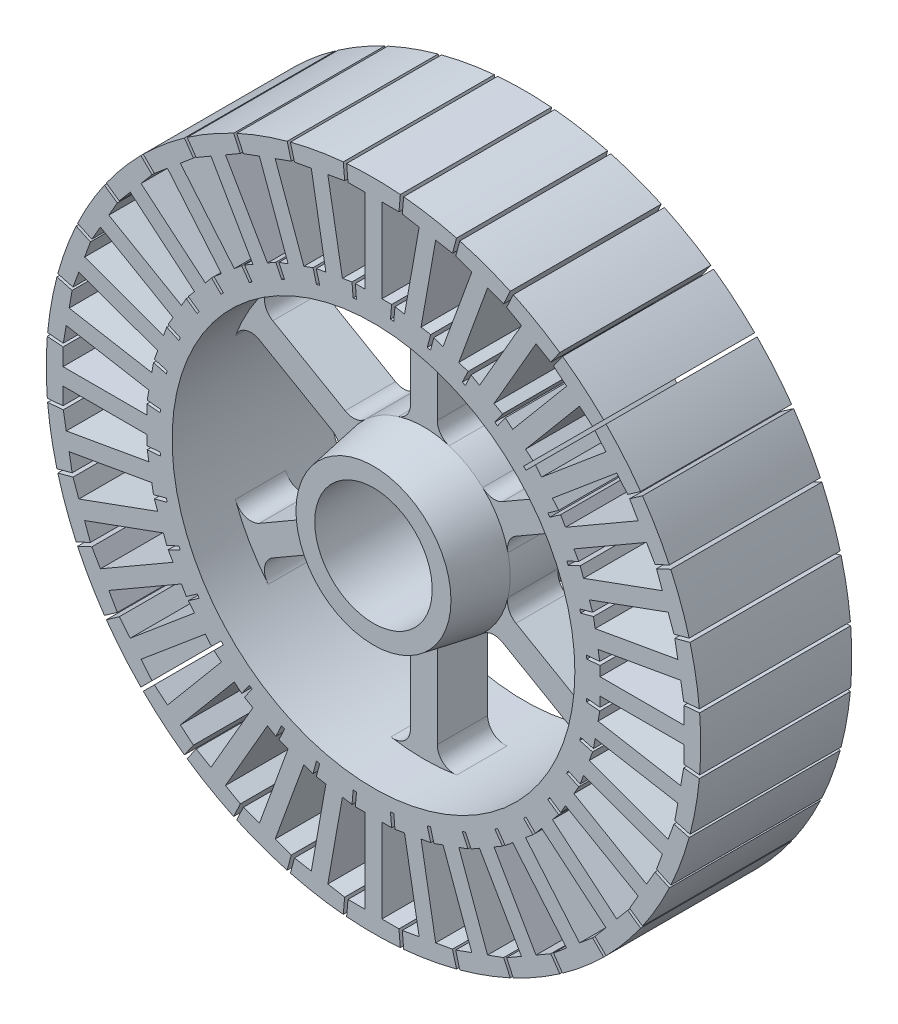
SolidWorks part; units mm, degrees
material "Нержавеющая сталь (ферритная)"
ref_plane "Спереди" through (0, 0, 0) normal (0, 0, 1) x (1, 0, 0)
ref_plane "Сверху" through (0, 0, 0) normal (0, 1, 0) x (1, 0, 0)
ref_plane "Справа" through (0, 0, 0) normal (1, 0, 0) x (0, 0, -1)
sketch "Эскиз1" plane through (0, 0, 0) normal (0, 0, 1) x (1, 0, 0)
  circle A0 centre (0, 0) radius 17.5
  circle A1 centre (0, 0) radius 97.5
  dimension "D1" = 35
  dimension "D2" = 195
extrude "Бобышка-Вытянуть1" add sketch "Эскиз1" along normal blind 45
sketch "Эскиз2" plane through (0, 0, 45) normal (0, 0, 1) x (1, 0, 0)
  line L0 (0, 0) -> (0, 97.5) construction
  line L1 (0, 0) -> (8.4977, 97.129) construction
  line L2 (0, 0) -> (-8.4977, 97.129) construction
  line L3 (-8.0518, 97.769) -> (-7.5908, 92.5)
  line L4 (-2.5, 92.5) -> (2.5, 92.5) construction
  line L5 (-2.5, 92.5) -> (-2.5, 67.5) construction
  line L6 (-2.5, 67.5) -> (2.5, 67.5) construction
  line L7 (2.5, 92.5) -> (2.5, 67.5) construction
  line L8 (0, 67.5) -> (0, 92.5) construction
  line L9 (-2.5, 80) -> (2.5, 80) construction
  line L10 (-7.5908, 92.5) -> (-2.5, 92.5)
  line L11 (-9.048, 97.6818) -> (-8.587, 92.4128)
  line L12 (-2.5, 67.5) -> (-5.4036, 67.5)
  line L13 (-5.4036, 67.5) -> (-5.0578, 63.5478)
  line L14 (-5.0578, 63.5478) -> (-6.054, 63.4607)
  line L15 (-2.5, 92.5) -> (-2.5, 67.5)
  line L16 (-8.587, 92.4128) -> (-13.6004, 91.5288)
  line L17 (-13.6004, 91.5288) -> (-9.2592, 66.9086)
  line L18 (-9.2592, 66.9086) -> (-6.3998, 67.4128)
  line L19 (-6.3998, 67.4128) -> (-6.054, 63.4607)
  line L20 (-8.0518, 97.769) -> (-9.048, 97.6818)
  line L21 (9.048, 97.6818) -> (8.0518, 97.769)
  line L22 (8.0518, 97.769) -> (7.5908, 92.5)
  line L23 (7.5908, 92.5) -> (2.5, 92.5)
  line L24 (2.5, 92.5) -> (2.5, 67.5)
  line L25 (2.5, 67.5) -> (5.4036, 67.5)
  line L26 (5.4036, 67.5) -> (5.0578, 63.5478)
  line L27 (6.054, 63.4607) -> (5.0578, 63.5478)
  line L28 (6.3998, 67.4128) -> (6.054, 63.4607)
  line L29 (9.2592, 66.9086) -> (6.3998, 67.4128)
  line L30 (13.6004, 91.5288) -> (9.2592, 66.9086)
  line L31 (8.587, 92.4128) -> (13.6004, 91.5288)
  line L32 (9.048, 97.6818) -> (8.587, 92.4128)
  line L33 (25.8728, 94.6267) -> (24.9068, 94.8855)
  line L34 (24.9068, 94.8855) -> (23.5379, 89.7766)
  line L35 (23.5379, 89.7766) -> (18.5245, 90.6606)
  line L36 (18.5245, 90.6606) -> (14.1833, 66.0404)
  line L37 (14.1833, 66.0404) -> (17.0427, 65.5362)
  line L38 (17.0427, 65.5362) -> (16.0159, 61.7041)
  line L39 (16.9819, 61.4453) -> (16.0159, 61.7041)
  line L40 (18.0087, 65.2774) -> (16.9819, 61.4453)
  line L41 (20.7371, 64.2843) -> (18.0087, 65.2774)
  line L42 (29.2876, 87.7766) -> (20.7371, 64.2843)
  line L43 (24.5039, 89.5178) -> (29.2876, 87.7766)
  line L44 (25.8728, 94.6267) -> (24.5039, 89.5178)
  line L45 (41.9115, 88.6963) -> (41.0051, 89.1189)
  line L46 (41.0051, 89.1189) -> (38.7699, 84.3254)
  line L47 (38.7699, 84.3254) -> (33.9861, 86.0665)
  line L48 (33.9861, 86.0665) -> (25.4356, 62.5742)
  line L49 (25.4356, 62.5742) -> (28.1641, 61.5811)
  line L50 (28.1641, 61.5811) -> (26.4874, 57.9856)
  line L51 (27.3937, 57.563) -> (26.4874, 57.9856)
  line L52 (29.0704, 61.1585) -> (27.3937, 57.563)
  line L53 (31.5849, 59.7067) -> (29.0704, 61.1585)
  line L54 (44.0849, 81.3573) -> (31.5849, 59.7067)
  line L55 (39.6762, 83.9027) -> (44.0849, 81.3573)
  line L56 (41.9115, 88.6963) -> (39.6762, 83.9027)
  line L57 (56.6767, 80.071) -> (55.8575, 80.6445)
  line L58 (55.8575, 80.6445) -> (52.8238, 76.312)
  line L59 (52.8238, 76.312) -> (48.4151, 78.8573)
  line L60 (48.4151, 78.8573) -> (35.9151, 57.2067)
  line L61 (35.9151, 57.2067) -> (38.4296, 55.7549)
  line L62 (38.4296, 55.7549) -> (36.1541, 52.5051)
  line L63 (36.9733, 51.9316) -> (36.1541, 52.5051)
  line L64 (39.2488, 55.1814) -> (36.9733, 51.9316)
  line L65 (41.4731, 53.315) -> (39.2488, 55.1814)
  line L66 (57.5427, 72.4661) -> (41.4731, 53.315)
  line L67 (53.643, 75.7384) -> (57.5427, 72.4661)
  line L68 (56.6767, 80.071) -> (53.643, 75.7384)
  line L69 (69.7198, 69.0127) -> (69.0127, 69.7198)
  line L70 (69.0127, 69.7198) -> (65.2727, 65.9798)
  line L71 (65.2727, 65.9798) -> (61.373, 69.2521)
  line L72 (61.373, 69.2521) -> (45.3033, 50.101)
  line L73 (45.3033, 50.101) -> (47.5275, 48.2346)
  line L74 (47.5275, 48.2346) -> (44.7223, 45.4294)
  line L75 (45.4294, 44.7223) -> (44.7223, 45.4294)
  line L76 (48.2346, 47.5275) -> (45.4294, 44.7223)
  line L77 (50.101, 45.3033) -> (48.2346, 47.5275)
  line L78 (69.2521, 61.373) -> (50.101, 45.3033)
  line L79 (65.9798, 65.2727) -> (69.2521, 61.373)
  line L80 (69.7198, 69.0127) -> (65.9798, 65.2727)
  line L81 (80.6445, 55.8575) -> (80.071, 56.6767)
  line L82 (80.071, 56.6767) -> (75.7384, 53.643)
  line L83 (75.7384, 53.643) -> (72.4661, 57.5427)
  line L84 (72.4661, 57.5427) -> (53.315, 41.4731)
  line L85 (53.315, 41.4731) -> (55.1814, 39.2488)
  line L86 (55.1814, 39.2488) -> (51.9316, 36.9733)
  line L87 (52.5051, 36.1541) -> (51.9316, 36.9733)
  line L88 (55.7549, 38.4296) -> (52.5051, 36.1541)
  line L89 (57.2067, 35.9151) -> (55.7549, 38.4296)
  line L90 (78.8573, 48.4151) -> (57.2067, 35.9151)
  line L91 (76.312, 52.8238) -> (78.8573, 48.4151)
  line L92 (80.6445, 55.8575) -> (76.312, 52.8238)
  line L93 (89.1189, 41.0051) -> (88.6963, 41.9115)
  line L94 (88.6963, 41.9115) -> (83.9027, 39.6762)
  line L95 (83.9027, 39.6762) -> (81.3573, 44.0849)
  line L96 (81.3573, 44.0849) -> (59.7067, 31.5849)
  line L97 (59.7067, 31.5849) -> (61.1585, 29.0704)
  line L98 (61.1585, 29.0704) -> (57.563, 27.3937)
  line L99 (57.9856, 26.4874) -> (57.563, 27.3937)
  line L100 (61.5811, 28.1641) -> (57.9856, 26.4874)
  line L101 (62.5742, 25.4356) -> (61.5811, 28.1641)
  line L102 (86.0665, 33.9861) -> (62.5742, 25.4356)
  line L103 (84.3254, 38.7699) -> (86.0665, 33.9861)
  line L104 (89.1189, 41.0051) -> (84.3254, 38.7699)
  line L105 (94.8855, 24.9068) -> (94.6267, 25.8728)
  line L106 (94.6267, 25.8728) -> (89.5178, 24.5039)
  line L107 (89.5178, 24.5039) -> (87.7766, 29.2876)
  line L108 (87.7766, 29.2876) -> (64.2843, 20.7371)
  line L109 (64.2843, 20.7371) -> (65.2774, 18.0087)
  line L110 (65.2774, 18.0087) -> (61.4453, 16.9819)
  line L111 (61.7041, 16.0159) -> (61.4453, 16.9819)
  line L112 (65.5362, 17.0427) -> (61.7041, 16.0159)
  line L113 (66.0404, 14.1833) -> (65.5362, 17.0427)
  line L114 (90.6606, 18.5245) -> (66.0404, 14.1833)
  line L115 (89.7766, 23.5379) -> (90.6606, 18.5245)
  line L116 (94.8855, 24.9068) -> (89.7766, 23.5379)
  line L117 (97.769, 8.0518) -> (97.6818, 9.048)
  line L118 (97.6818, 9.048) -> (92.4128, 8.587)
  line L119 (92.4128, 8.587) -> (91.5288, 13.6004)
  line L120 (91.5288, 13.6004) -> (66.9086, 9.2592)
  line L121 (66.9086, 9.2592) -> (67.4128, 6.3998)
  line L122 (67.4128, 6.3998) -> (63.4607, 6.054)
  line L123 (63.5478, 5.0578) -> (63.4607, 6.054)
  line L124 (67.5, 5.4036) -> (63.5478, 5.0578)
  line L125 (67.5, 2.5) -> (67.5, 5.4036)
  line L126 (92.5, 2.5) -> (67.5, 2.5)
  line L127 (92.5, 7.5908) -> (92.5, 2.5)
  line L128 (97.769, 8.0518) -> (92.5, 7.5908)
  line L129 (97.6818, -9.048) -> (97.769, -8.0518)
  line L130 (97.769, -8.0518) -> (92.5, -7.5908)
  line L131 (92.5, -7.5908) -> (92.5, -2.5)
  line L132 (92.5, -2.5) -> (67.5, -2.5)
  line L133 (67.5, -2.5) -> (67.5, -5.4036)
  line L134 (67.5, -5.4036) -> (63.5478, -5.0578)
  line L135 (63.4607, -6.054) -> (63.5478, -5.0578)
  line L136 (67.4128, -6.3998) -> (63.4607, -6.054)
  line L137 (66.9086, -9.2592) -> (67.4128, -6.3998)
  line L138 (91.5288, -13.6004) -> (66.9086, -9.2592)
  line L139 (92.4128, -8.587) -> (91.5288, -13.6004)
  line L140 (97.6818, -9.048) -> (92.4128, -8.587)
  line L141 (94.6267, -25.8728) -> (94.8855, -24.9068)
  line L142 (94.8855, -24.9068) -> (89.7766, -23.5379)
  line L143 (89.7766, -23.5379) -> (90.6606, -18.5245)
  line L144 (90.6606, -18.5245) -> (66.0404, -14.1833)
  line L145 (66.0404, -14.1833) -> (65.5362, -17.0427)
  line L146 (65.5362, -17.0427) -> (61.7041, -16.0159)
  line L147 (61.4453, -16.9819) -> (61.7041, -16.0159)
  line L148 (65.2774, -18.0087) -> (61.4453, -16.9819)
  line L149 (64.2843, -20.7371) -> (65.2774, -18.0087)
  line L150 (87.7766, -29.2876) -> (64.2843, -20.7371)
  line L151 (89.5178, -24.5039) -> (87.7766, -29.2876)
  line L152 (94.6267, -25.8728) -> (89.5178, -24.5039)
  line L153 (88.6963, -41.9115) -> (89.1189, -41.0051)
  line L154 (89.1189, -41.0051) -> (84.3254, -38.7699)
  line L155 (84.3254, -38.7699) -> (86.0665, -33.9861)
  line L156 (86.0665, -33.9861) -> (62.5742, -25.4356)
  line L157 (62.5742, -25.4356) -> (61.5811, -28.1641)
  line L158 (61.5811, -28.1641) -> (57.9856, -26.4874)
  line L159 (57.563, -27.3937) -> (57.9856, -26.4874)
  line L160 (61.1585, -29.0704) -> (57.563, -27.3937)
  line L161 (59.7067, -31.5849) -> (61.1585, -29.0704)
  line L162 (81.3573, -44.0849) -> (59.7067, -31.5849)
  line L163 (83.9027, -39.6762) -> (81.3573, -44.0849)
  line L164 (88.6963, -41.9115) -> (83.9027, -39.6762)
  line L165 (80.071, -56.6767) -> (80.6445, -55.8575)
  line L166 (80.6445, -55.8575) -> (76.312, -52.8238)
  line L167 (76.312, -52.8238) -> (78.8573, -48.4151)
  line L168 (78.8573, -48.4151) -> (57.2067, -35.9151)
  line L169 (57.2067, -35.9151) -> (55.7549, -38.4296)
  line L170 (55.7549, -38.4296) -> (52.5051, -36.1541)
  line L171 (51.9316, -36.9733) -> (52.5051, -36.1541)
  line L172 (55.1814, -39.2488) -> (51.9316, -36.9733)
  line L173 (53.315, -41.4731) -> (55.1814, -39.2488)
  line L174 (72.4661, -57.5427) -> (53.315, -41.4731)
  line L175 (75.7384, -53.643) -> (72.4661, -57.5427)
  line L176 (80.071, -56.6767) -> (75.7384, -53.643)
  line L177 (69.0127, -69.7198) -> (69.7198, -69.0127)
  line L178 (69.7198, -69.0127) -> (65.9798, -65.2727)
  line L179 (65.9798, -65.2727) -> (69.2521, -61.373)
  line L180 (69.2521, -61.373) -> (50.101, -45.3033)
  line L181 (50.101, -45.3033) -> (48.2346, -47.5275)
  line L182 (48.2346, -47.5275) -> (45.4294, -44.7223)
  line L183 (44.7223, -45.4294) -> (45.4294, -44.7223)
  line L184 (47.5275, -48.2346) -> (44.7223, -45.4294)
  line L185 (45.3033, -50.101) -> (47.5275, -48.2346)
  line L186 (61.373, -69.2521) -> (45.3033, -50.101)
  line L187 (65.2727, -65.9798) -> (61.373, -69.2521)
  line L188 (69.0127, -69.7198) -> (65.2727, -65.9798)
  line L189 (55.8575, -80.6445) -> (56.6767, -80.071)
  line L190 (56.6767, -80.071) -> (53.643, -75.7384)
  line L191 (53.643, -75.7384) -> (57.5427, -72.4661)
  line L192 (57.5427, -72.4661) -> (41.4731, -53.315)
  line L193 (41.4731, -53.315) -> (39.2488, -55.1814)
  line L194 (39.2488, -55.1814) -> (36.9733, -51.9316)
  line L195 (36.1541, -52.5051) -> (36.9733, -51.9316)
  line L196 (38.4296, -55.7549) -> (36.1541, -52.5051)
  line L197 (35.9151, -57.2067) -> (38.4296, -55.7549)
  line L198 (48.4151, -78.8573) -> (35.9151, -57.2067)
  line L199 (52.8238, -76.312) -> (48.4151, -78.8573)
  line L200 (55.8575, -80.6445) -> (52.8238, -76.312)
  line L201 (41.0051, -89.1189) -> (41.9115, -88.6963)
  line L202 (41.9115, -88.6963) -> (39.6762, -83.9027)
  line L203 (39.6762, -83.9027) -> (44.0849, -81.3573)
  line L204 (44.0849, -81.3573) -> (31.5849, -59.7067)
  line L205 (31.5849, -59.7067) -> (29.0704, -61.1585)
  line L206 (29.0704, -61.1585) -> (27.3937, -57.563)
  line L207 (26.4874, -57.9856) -> (27.3937, -57.563)
  line L208 (28.1641, -61.5811) -> (26.4874, -57.9856)
  line L209 (25.4356, -62.5742) -> (28.1641, -61.5811)
  line L210 (33.9861, -86.0665) -> (25.4356, -62.5742)
  line L211 (38.7699, -84.3254) -> (33.9861, -86.0665)
  line L212 (41.0051, -89.1189) -> (38.7699, -84.3254)
  line L213 (24.9068, -94.8855) -> (25.8728, -94.6267)
  line L214 (25.8728, -94.6267) -> (24.5039, -89.5178)
  line L215 (24.5039, -89.5178) -> (29.2876, -87.7766)
  line L216 (29.2876, -87.7766) -> (20.7371, -64.2843)
  line L217 (20.7371, -64.2843) -> (18.0087, -65.2774)
  line L218 (18.0087, -65.2774) -> (16.9819, -61.4453)
  line L219 (16.0159, -61.7041) -> (16.9819, -61.4453)
  line L220 (17.0427, -65.5362) -> (16.0159, -61.7041)
  line L221 (14.1833, -66.0404) -> (17.0427, -65.5362)
  line L222 (18.5245, -90.6606) -> (14.1833, -66.0404)
  line L223 (23.5379, -89.7766) -> (18.5245, -90.6606)
  line L224 (24.9068, -94.8855) -> (23.5379, -89.7766)
  line L225 (8.0518, -97.769) -> (9.048, -97.6818)
  line L226 (9.048, -97.6818) -> (8.587, -92.4128)
  line L227 (8.587, -92.4128) -> (13.6004, -91.5288)
  line L228 (13.6004, -91.5288) -> (9.2592, -66.9086)
  line L229 (9.2592, -66.9086) -> (6.3998, -67.4128)
  line L230 (6.3998, -67.4128) -> (6.054, -63.4607)
  line L231 (5.0578, -63.5478) -> (6.054, -63.4607)
  line L232 (5.4036, -67.5) -> (5.0578, -63.5478)
  line L233 (2.5, -67.5) -> (5.4036, -67.5)
  line L234 (2.5, -92.5) -> (2.5, -67.5)
  line L235 (7.5908, -92.5) -> (2.5, -92.5)
  line L236 (8.0518, -97.769) -> (7.5908, -92.5)
  line L237 (-9.048, -97.6818) -> (-8.0518, -97.769)
  line L238 (-8.0518, -97.769) -> (-7.5908, -92.5)
  line L239 (-7.5908, -92.5) -> (-2.5, -92.5)
  line L240 (-2.5, -92.5) -> (-2.5, -67.5)
  line L241 (-2.5, -67.5) -> (-5.4036, -67.5)
  line L242 (-5.4036, -67.5) -> (-5.0578, -63.5478)
  line L243 (-6.054, -63.4607) -> (-5.0578, -63.5478)
  line L244 (-6.3998, -67.4128) -> (-6.054, -63.4607)
  line L245 (-9.2592, -66.9086) -> (-6.3998, -67.4128)
  line L246 (-13.6004, -91.5288) -> (-9.2592, -66.9086)
  line L247 (-8.587, -92.4128) -> (-13.6004, -91.5288)
  line L248 (-9.048, -97.6818) -> (-8.587, -92.4128)
  line L249 (-25.8728, -94.6267) -> (-24.9068, -94.8855)
  line L250 (-24.9068, -94.8855) -> (-23.5379, -89.7766)
  line L251 (-23.5379, -89.7766) -> (-18.5245, -90.6606)
  line L252 (-18.5245, -90.6606) -> (-14.1833, -66.0404)
  line L253 (-14.1833, -66.0404) -> (-17.0427, -65.5362)
  line L254 (-17.0427, -65.5362) -> (-16.0159, -61.7041)
  line L255 (-16.9819, -61.4453) -> (-16.0159, -61.7041)
  line L256 (-18.0087, -65.2774) -> (-16.9819, -61.4453)
  line L257 (-20.7371, -64.2843) -> (-18.0087, -65.2774)
  line L258 (-29.2876, -87.7766) -> (-20.7371, -64.2843)
  line L259 (-24.5039, -89.5178) -> (-29.2876, -87.7766)
  line L260 (-25.8728, -94.6267) -> (-24.5039, -89.5178)
  line L261 (-41.9115, -88.6963) -> (-41.0051, -89.1189)
  line L262 (-41.0051, -89.1189) -> (-38.7699, -84.3254)
  line L263 (-38.7699, -84.3254) -> (-33.9861, -86.0665)
  line L264 (-33.9861, -86.0665) -> (-25.4356, -62.5742)
  line L265 (-25.4356, -62.5742) -> (-28.1641, -61.5811)
  line L266 (-28.1641, -61.5811) -> (-26.4874, -57.9856)
  line L267 (-27.3937, -57.563) -> (-26.4874, -57.9856)
  line L268 (-29.0704, -61.1585) -> (-27.3937, -57.563)
  line L269 (-31.5849, -59.7067) -> (-29.0704, -61.1585)
  line L270 (-44.0849, -81.3573) -> (-31.5849, -59.7067)
  line L271 (-39.6762, -83.9027) -> (-44.0849, -81.3573)
  line L272 (-41.9115, -88.6963) -> (-39.6762, -83.9027)
  line L273 (-56.6767, -80.071) -> (-55.8575, -80.6445)
  line L274 (-55.8575, -80.6445) -> (-52.8238, -76.312)
  line L275 (-52.8238, -76.312) -> (-48.4151, -78.8573)
  line L276 (-48.4151, -78.8573) -> (-35.9151, -57.2067)
  line L277 (-35.9151, -57.2067) -> (-38.4296, -55.7549)
  line L278 (-38.4296, -55.7549) -> (-36.1541, -52.5051)
  line L279 (-36.9733, -51.9316) -> (-36.1541, -52.5051)
  line L280 (-39.2488, -55.1814) -> (-36.9733, -51.9316)
  line L281 (-41.4731, -53.315) -> (-39.2488, -55.1814)
  line L282 (-57.5427, -72.4661) -> (-41.4731, -53.315)
  line L283 (-53.643, -75.7384) -> (-57.5427, -72.4661)
  line L284 (-56.6767, -80.071) -> (-53.643, -75.7384)
  line L285 (-69.7198, -69.0127) -> (-69.0127, -69.7198)
  line L286 (-69.0127, -69.7198) -> (-65.2727, -65.9798)
  line L287 (-65.2727, -65.9798) -> (-61.373, -69.2521)
  line L288 (-61.373, -69.2521) -> (-45.3033, -50.101)
  line L289 (-45.3033, -50.101) -> (-47.5275, -48.2346)
  line L290 (-47.5275, -48.2346) -> (-44.7223, -45.4294)
  line L291 (-45.4294, -44.7223) -> (-44.7223, -45.4294)
  line L292 (-48.2346, -47.5275) -> (-45.4294, -44.7223)
  line L293 (-50.101, -45.3033) -> (-48.2346, -47.5275)
  line L294 (-69.2521, -61.373) -> (-50.101, -45.3033)
  line L295 (-65.9798, -65.2727) -> (-69.2521, -61.373)
  line L296 (-69.7198, -69.0127) -> (-65.9798, -65.2727)
  line L297 (-80.6445, -55.8575) -> (-80.071, -56.6767)
  line L298 (-80.071, -56.6767) -> (-75.7384, -53.643)
  line L299 (-75.7384, -53.643) -> (-72.4661, -57.5427)
  line L300 (-72.4661, -57.5427) -> (-53.315, -41.4731)
  line L301 (-53.315, -41.4731) -> (-55.1814, -39.2488)
  line L302 (-55.1814, -39.2488) -> (-51.9316, -36.9733)
  line L303 (-52.5051, -36.1541) -> (-51.9316, -36.9733)
  line L304 (-55.7549, -38.4296) -> (-52.5051, -36.1541)
  line L305 (-57.2067, -35.9151) -> (-55.7549, -38.4296)
  line L306 (-78.8573, -48.4151) -> (-57.2067, -35.9151)
  line L307 (-76.312, -52.8238) -> (-78.8573, -48.4151)
  line L308 (-80.6445, -55.8575) -> (-76.312, -52.8238)
  line L309 (-89.1189, -41.0051) -> (-88.6963, -41.9115)
  line L310 (-88.6963, -41.9115) -> (-83.9027, -39.6762)
  line L311 (-83.9027, -39.6762) -> (-81.3573, -44.0849)
  line L312 (-81.3573, -44.0849) -> (-59.7067, -31.5849)
  line L313 (-59.7067, -31.5849) -> (-61.1585, -29.0704)
  line L314 (-61.1585, -29.0704) -> (-57.563, -27.3937)
  line L315 (-57.9856, -26.4874) -> (-57.563, -27.3937)
  line L316 (-61.5811, -28.1641) -> (-57.9856, -26.4874)
  line L317 (-62.5742, -25.4356) -> (-61.5811, -28.1641)
  line L318 (-86.0665, -33.9861) -> (-62.5742, -25.4356)
  line L319 (-84.3254, -38.7699) -> (-86.0665, -33.9861)
  line L320 (-89.1189, -41.0051) -> (-84.3254, -38.7699)
  line L321 (-94.8855, -24.9068) -> (-94.6267, -25.8728)
  line L322 (-94.6267, -25.8728) -> (-89.5178, -24.5039)
  line L323 (-89.5178, -24.5039) -> (-87.7766, -29.2876)
  line L324 (-87.7766, -29.2876) -> (-64.2843, -20.7371)
  line L325 (-64.2843, -20.7371) -> (-65.2774, -18.0087)
  line L326 (-65.2774, -18.0087) -> (-61.4453, -16.9819)
  line L327 (-61.7041, -16.0159) -> (-61.4453, -16.9819)
  line L328 (-65.5362, -17.0427) -> (-61.7041, -16.0159)
  line L329 (-66.0404, -14.1833) -> (-65.5362, -17.0427)
  line L330 (-90.6606, -18.5245) -> (-66.0404, -14.1833)
  line L331 (-89.7766, -23.5379) -> (-90.6606, -18.5245)
  line L332 (-94.8855, -24.9068) -> (-89.7766, -23.5379)
  line L333 (-97.769, -8.0518) -> (-97.6818, -9.048)
  line L334 (-97.6818, -9.048) -> (-92.4128, -8.587)
  line L335 (-92.4128, -8.587) -> (-91.5288, -13.6004)
  line L336 (-91.5288, -13.6004) -> (-66.9086, -9.2592)
  line L337 (-66.9086, -9.2592) -> (-67.4128, -6.3998)
  line L338 (-67.4128, -6.3998) -> (-63.4607, -6.054)
  line L339 (-63.5478, -5.0578) -> (-63.4607, -6.054)
  line L340 (-67.5, -5.4036) -> (-63.5478, -5.0578)
  line L341 (-67.5, -2.5) -> (-67.5, -5.4036)
  line L342 (-92.5, -2.5) -> (-67.5, -2.5)
  line L343 (-92.5, -7.5908) -> (-92.5, -2.5)
  line L344 (-97.769, -8.0518) -> (-92.5, -7.5908)
  line L345 (-97.6818, 9.048) -> (-97.769, 8.0518)
  line L346 (-97.769, 8.0518) -> (-92.5, 7.5908)
  line L347 (-92.5, 7.5908) -> (-92.5, 2.5)
  line L348 (-92.5, 2.5) -> (-67.5, 2.5)
  line L349 (-67.5, 2.5) -> (-67.5, 5.4036)
  line L350 (-67.5, 5.4036) -> (-63.5478, 5.0578)
  line L351 (-63.4607, 6.054) -> (-63.5478, 5.0578)
  line L352 (-67.4128, 6.3998) -> (-63.4607, 6.054)
  line L353 (-66.9086, 9.2592) -> (-67.4128, 6.3998)
  line L354 (-91.5288, 13.6004) -> (-66.9086, 9.2592)
  line L355 (-92.4128, 8.587) -> (-91.5288, 13.6004)
  line L356 (-97.6818, 9.048) -> (-92.4128, 8.587)
  line L357 (-94.6267, 25.8728) -> (-94.8855, 24.9068)
  line L358 (-94.8855, 24.9068) -> (-89.7766, 23.5379)
  line L359 (-89.7766, 23.5379) -> (-90.6606, 18.5245)
  line L360 (-90.6606, 18.5245) -> (-66.0404, 14.1833)
  line L361 (-66.0404, 14.1833) -> (-65.5362, 17.0427)
  line L362 (-65.5362, 17.0427) -> (-61.7041, 16.0159)
  line L363 (-61.4453, 16.9819) -> (-61.7041, 16.0159)
  line L364 (-65.2774, 18.0087) -> (-61.4453, 16.9819)
  line L365 (-64.2843, 20.7371) -> (-65.2774, 18.0087)
  line L366 (-87.7766, 29.2876) -> (-64.2843, 20.7371)
  line L367 (-89.5178, 24.5039) -> (-87.7766, 29.2876)
  line L368 (-94.6267, 25.8728) -> (-89.5178, 24.5039)
  line L369 (-88.6963, 41.9115) -> (-89.1189, 41.0051)
  line L370 (-89.1189, 41.0051) -> (-84.3254, 38.7699)
  line L371 (-84.3254, 38.7699) -> (-86.0665, 33.9861)
  line L372 (-86.0665, 33.9861) -> (-62.5742, 25.4356)
  line L373 (-62.5742, 25.4356) -> (-61.5811, 28.1641)
  line L374 (-61.5811, 28.1641) -> (-57.9856, 26.4874)
  line L375 (-57.563, 27.3937) -> (-57.9856, 26.4874)
  line L376 (-61.1585, 29.0704) -> (-57.563, 27.3937)
  line L377 (-59.7067, 31.5849) -> (-61.1585, 29.0704)
  line L378 (-81.3573, 44.0849) -> (-59.7067, 31.5849)
  line L379 (-83.9027, 39.6762) -> (-81.3573, 44.0849)
  line L380 (-88.6963, 41.9115) -> (-83.9027, 39.6762)
  line L381 (-80.071, 56.6767) -> (-80.6445, 55.8575)
  line L382 (-80.6445, 55.8575) -> (-76.312, 52.8238)
  line L383 (-76.312, 52.8238) -> (-78.8573, 48.4151)
  line L384 (-78.8573, 48.4151) -> (-57.2067, 35.9151)
  line L385 (-57.2067, 35.9151) -> (-55.7549, 38.4296)
  line L386 (-55.7549, 38.4296) -> (-52.5051, 36.1541)
  line L387 (-51.9316, 36.9733) -> (-52.5051, 36.1541)
  line L388 (-55.1814, 39.2488) -> (-51.9316, 36.9733)
  line L389 (-53.315, 41.4731) -> (-55.1814, 39.2488)
  line L390 (-72.4661, 57.5427) -> (-53.315, 41.4731)
  line L391 (-75.7384, 53.643) -> (-72.4661, 57.5427)
  line L392 (-80.071, 56.6767) -> (-75.7384, 53.643)
  line L393 (-69.0127, 69.7198) -> (-69.7198, 69.0127)
  line L394 (-69.7198, 69.0127) -> (-65.9798, 65.2727)
  line L395 (-65.9798, 65.2727) -> (-69.2521, 61.373)
  line L396 (-69.2521, 61.373) -> (-50.101, 45.3033)
  line L397 (-50.101, 45.3033) -> (-48.2346, 47.5275)
  line L398 (-48.2346, 47.5275) -> (-45.4294, 44.7223)
  line L399 (-44.7223, 45.4294) -> (-45.4294, 44.7223)
  line L400 (-47.5275, 48.2346) -> (-44.7223, 45.4294)
  line L401 (-45.3033, 50.101) -> (-47.5275, 48.2346)
  line L402 (-61.373, 69.2521) -> (-45.3033, 50.101)
  line L403 (-65.2727, 65.9798) -> (-61.373, 69.2521)
  line L404 (-69.0127, 69.7198) -> (-65.2727, 65.9798)
  line L405 (-55.8575, 80.6445) -> (-56.6767, 80.071)
  line L406 (-56.6767, 80.071) -> (-53.643, 75.7384)
  line L407 (-53.643, 75.7384) -> (-57.5427, 72.4661)
  line L408 (-57.5427, 72.4661) -> (-41.4731, 53.315)
  line L409 (-41.4731, 53.315) -> (-39.2488, 55.1814)
  line L410 (-39.2488, 55.1814) -> (-36.9733, 51.9316)
  line L411 (-36.1541, 52.5051) -> (-36.9733, 51.9316)
  line L412 (-38.4296, 55.7549) -> (-36.1541, 52.5051)
  line L413 (-35.9151, 57.2067) -> (-38.4296, 55.7549)
  line L414 (-48.4151, 78.8573) -> (-35.9151, 57.2067)
  line L415 (-52.8238, 76.312) -> (-48.4151, 78.8573)
  line L416 (-55.8575, 80.6445) -> (-52.8238, 76.312)
  line L417 (-41.0051, 89.1189) -> (-41.9115, 88.6963)
  line L418 (-41.9115, 88.6963) -> (-39.6762, 83.9027)
  line L419 (-39.6762, 83.9027) -> (-44.0849, 81.3573)
  line L420 (-44.0849, 81.3573) -> (-31.5849, 59.7067)
  line L421 (-31.5849, 59.7067) -> (-29.0704, 61.1585)
  line L422 (-29.0704, 61.1585) -> (-27.3937, 57.563)
  line L423 (-26.4874, 57.9856) -> (-27.3937, 57.563)
  line L424 (-28.1641, 61.5811) -> (-26.4874, 57.9856)
  line L425 (-25.4356, 62.5742) -> (-28.1641, 61.5811)
  line L426 (-33.9861, 86.0665) -> (-25.4356, 62.5742)
  line L427 (-38.7699, 84.3254) -> (-33.9861, 86.0665)
  line L428 (-41.0051, 89.1189) -> (-38.7699, 84.3254)
  line L429 (-24.9068, 94.8855) -> (-25.8728, 94.6267)
  line L430 (-25.8728, 94.6267) -> (-24.5039, 89.5178)
  line L431 (-24.5039, 89.5178) -> (-29.2876, 87.7766)
  line L432 (-29.2876, 87.7766) -> (-20.7371, 64.2843)
  line L433 (-20.7371, 64.2843) -> (-18.0087, 65.2774)
  line L434 (-18.0087, 65.2774) -> (-16.9819, 61.4453)
  line L435 (-16.0159, 61.7041) -> (-16.9819, 61.4453)
  line L436 (-17.0427, 65.5362) -> (-16.0159, 61.7041)
  line L437 (-14.1833, 66.0404) -> (-17.0427, 65.5362)
  line L438 (-18.5245, 90.6606) -> (-14.1833, 66.0404)
  line L439 (-23.5379, 89.7766) -> (-18.5245, 90.6606)
  line L440 (-24.9068, 94.8855) -> (-23.5379, 89.7766)
  circle A0 centre (0, 0) radius 97.5 construction
  point P6 (0, 80)
  point P26 (-5.5559, 63.5043)
  point P451 (0, 0)
  dimension "D6" = 0.5
  dimension "D1" = 5
  dimension "D2" = 5
  dimension "D3" = 25
  dimension "D4" = 5
  dimension "D5" = 5
  dimension "D7" = 0.5
  dimension "D8" = 36
extrude "Вырез-Вытянуть1" cut sketch "Эскиз2" against normal through all
sketch "Эскиз3" plane through (0, 0, 45) normal (0, 0, 1) x (1, 0, 0)
  circle A0 centre (0, 0) radius 60
  circle A1 centre (0, 0) radius 27.5
  dimension "D1" = 120
  dimension "D2" = 55
extrude "Вырез-Вытянуть2" cut sketch "Эскиз3" against normal blind 15
sketch "Эскиз4" plane through (0, 0, 0) normal (0, 0, -1) x (-1, 0, 0)
  circle A0 centre (0, 0) radius 60
  circle A1 centre (0, 0) radius 27.5
  dimension "D1" = 120
  dimension "D2" = 55
extrude "Вырез-Вытянуть3" cut sketch "Эскиз4" against normal blind 15
chamfer "Фаска1" distance 25 angle 10 2 edges at (-27.5, 0, 0) (27.5, 0, 45) first distance on face at (-27.5, 0, 15) first distance on face at (27.5, 0, 30)
sketch "Эскиз6" plane through (0, 0, 30) normal (0, 0, 1) x (1, 0, 0)
  line L0 (0, 0) -> (0, 60) construction
  line L1 (0, 0) -> (51.9615, 30) construction
  line L2 (0, 25.7367) -> (0, 60) construction
  line L3 (22.2887, 12.8684) -> (51.9615, 30) construction
  line L4 (4, 29.3896) -> (4, 54.2586)
  line L5 (23.4521, 18.1589) -> (44.9894, 30.5934)
  line L6 (27.4521, -11.2307) -> (48.9894, -23.6652)
  line L7 (27.4521, 11.2307) -> (48.9894, 23.6652)
  line L8 (4, -29.3896) -> (4, -54.2586)
  line L9 (23.4521, -18.1589) -> (44.9894, -30.5934)
  line L10 (-23.4521, -18.1589) -> (-44.9894, -30.5934)
  line L11 (-4, -29.3896) -> (-4, -54.2586)
  line L12 (-27.4521, 11.2307) -> (-48.9894, 23.6652)
  line L13 (-27.4521, -11.2307) -> (-48.9894, -23.6652)
  line L14 (-4, 29.3896) -> (-4, 54.2586)
  line L15 (-23.4521, 18.1589) -> (-44.9894, 30.5934)
  circle A0 centre (0, 0) radius 60 construction
  arc A1 (0, 25.7367) -> (22.2887, 12.8684) centre (0, 0) cw construction
  circle A2 centre (0, 0) radius 25.7367 construction
  arc A3 (0, 60) -> (51.9615, 30) centre (0, 0) cw construction
  arc A4 (7.536, 24.6087) -> (17.5438, 18.8307) centre (0, 0) cw
  arc A5 (9.8182, 59.1912) -> (46.352, 38.0984) centre (0, 0) cw
  arc A6 (4, 29.3896) -> (7.536, 24.6087) centre (9, 29.3896) ccw
  arc A7 (23.4521, 18.1589) -> (17.5438, 18.8307) centre (20.9521, 22.489) cw
  arc A8 (44.9894, 30.5934) -> (46.352, 38.0984) centre (42.4894, 34.9235) ccw
  arc A9 (4, 54.2586) -> (9.8182, 59.1912) centre (9, 54.2586) cw
  arc A10 (56.1702, 21.0928) -> (56.1702, -21.0928) centre (0, 0) cw
  arc A11 (48.9894, 23.6652) -> (56.1702, 21.0928) centre (51.4894, 19.3351) cw
  arc A12 (48.9894, -23.6652) -> (56.1702, -21.0928) centre (51.4894, -19.3351) ccw
  arc A13 (27.4521, -11.2307) -> (25.0797, -5.778) centre (29.9521, -6.9006) cw
  arc A14 (25.0797, 5.778) -> (25.0797, -5.778) centre (0, 0) cw
  arc A15 (27.4521, 11.2307) -> (25.0797, 5.778) centre (29.9521, 6.9006) ccw
  arc A16 (46.352, -38.0984) -> (9.8182, -59.1912) centre (0, 0) cw
  arc A17 (44.9894, -30.5934) -> (46.352, -38.0984) centre (42.4894, -34.9235) cw
  arc A18 (4, -54.2586) -> (9.8182, -59.1912) centre (9, -54.2586) ccw
  arc A19 (4, -29.3896) -> (7.536, -24.6087) centre (9, -29.3896) cw
  arc A20 (17.5438, -18.8307) -> (7.536, -24.6087) centre (0, 0) cw
  arc A21 (23.4521, -18.1589) -> (17.5438, -18.8307) centre (20.9521, -22.489) ccw
  arc A22 (-9.8182, -59.1912) -> (-46.352, -38.0984) centre (0, 0) cw
  arc A23 (-4, -54.2586) -> (-9.8182, -59.1912) centre (-9, -54.2586) cw
  arc A24 (-44.9894, -30.5934) -> (-46.352, -38.0984) centre (-42.4894, -34.9235) ccw
  arc A25 (-23.4521, -18.1589) -> (-17.5438, -18.8307) centre (-20.9521, -22.489) cw
  arc A26 (-7.536, -24.6087) -> (-17.5438, -18.8307) centre (0, 0) cw
  arc A27 (-4, -29.3896) -> (-7.536, -24.6087) centre (-9, -29.3896) ccw
  arc A28 (-56.1702, -21.0928) -> (-56.1702, 21.0928) centre (0, 0) cw
  arc A29 (-48.9894, -23.6652) -> (-56.1702, -21.0928) centre (-51.4894, -19.3351) cw
  arc A30 (-48.9894, 23.6652) -> (-56.1702, 21.0928) centre (-51.4894, 19.3351) ccw
  arc A31 (-27.4521, 11.2307) -> (-25.0797, 5.778) centre (-29.9521, 6.9006) cw
  arc A32 (-25.0797, -5.778) -> (-25.0797, 5.778) centre (0, 0) cw
  arc A33 (-27.4521, -11.2307) -> (-25.0797, -5.778) centre (-29.9521, -6.9006) ccw
  arc A34 (-46.352, 38.0984) -> (-9.8182, 59.1912) centre (0, 0) cw
  arc A35 (-44.9894, 30.5934) -> (-46.352, 38.0984) centre (-42.4894, 34.9235) cw
  arc A36 (-4, 54.2586) -> (-9.8182, 59.1912) centre (-9, 54.2586) ccw
  arc A37 (-4, 29.3896) -> (-7.536, 24.6087) centre (-9, 29.3896) cw
  arc A38 (-17.5438, 18.8307) -> (-7.536, 24.6087) centre (0, 0) cw
  arc A39 (-23.4521, 18.1589) -> (-17.5438, 18.8307) centre (-20.9521, 22.489) ccw
  point P21 (4, 25.424)
  point P24 (20.0178, 16.1761)
  point P27 (49.8459, 33.3974)
  point P30 (4, 59.8665)
  point P93 (0, 0)
  dimension "D2" = 4
  dimension "D4" = 5
  dimension "D1" = 60
  dimension "D3" = 4
  dimension "D5" = 6
extrude "Вырез-Вытянуть4" cut sketch "Эскиз6" against normal through all
